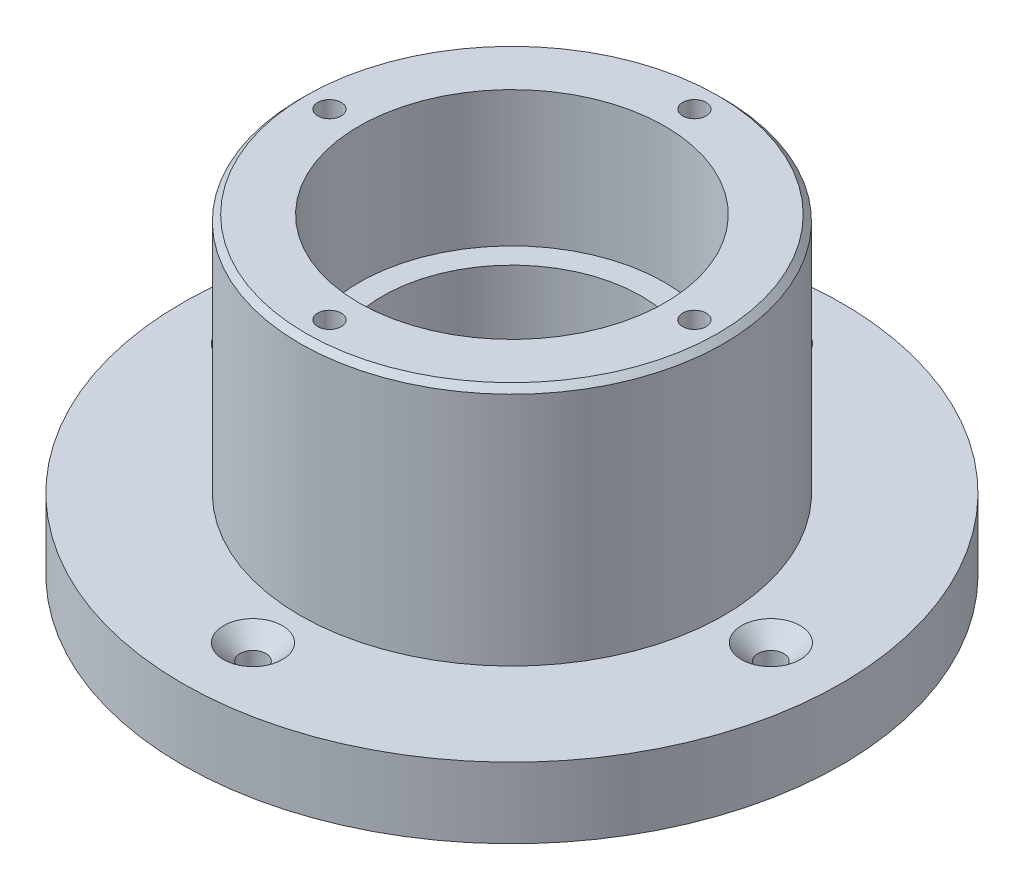
SolidWorks part; units mm, degrees
material "ABS"
ref_plane "Спереди" through (0, 0, 0) normal (0, 0, 1) x (1, 0, 0)
ref_plane "Сверху" through (0, 0, 0) normal (0, 1, 0) x (1, 0, 0)
ref_plane "Справа" through (0, 0, 0) normal (1, 0, 0) x (0, 0, -1)
sketch "Эскиз1" plane through (0, 0, 0) normal (0, 1, 0) x (1, 0, 0)
  circle A0 centre (0, 0) radius 26
  dimension "D1" = 52
extrude "Бобышка-Вытянуть1" add sketch "Эскиз1" along normal blind 4
sketch "Эскиз2" plane through (0, 4, 0) normal (0, 1, 0) x (1, 0, 0)
  circle A0 centre (0, 0) radius 18
  dimension "D1" = 36
extrude "Бобышка-Вытянуть2" add sketch "Эскиз2" along normal blind 20.5
sketch "Эскиз3" plane through (0, 24.5, 0) normal (0, 1, 0) x (1, 0, 0)
  circle A0 centre (0, 0) radius 13
  dimension "D1" = 26
extrude "Вырез-Вытянуть1" cut sketch "Эскиз3" along direction (0, 1, 0) on the side against the normal offset from surface (11.5 mm away) 13 up to face at (0, 0, 26)
sketch "Эскиз4" plane through (0, 4, 0) normal (0, 1, 0) x (1, 0, 0)
  circle A0 centre (0, 0) radius 22 construction
  circle A1 centre (-22, 0) radius 2.2
  circle A2 centre (0, 22) radius 2.2
  circle A3 centre (22, 0) radius 2.2
  circle A4 centre (0, -22) radius 2.2
  point P14 (0, 0)
  dimension "D1" = 44
  dimension "D2" = 4.4
  dimension "D3" = 4
sketch "Эскиз6" plane through (0, 13, 0) normal (0, 1, 0) x (1, 0, 0)
  circle A0 centre (0, 0) radius 11
  dimension "D1" = 22
extrude "Вырез-Вытянуть4" cut sketch "Эскиз6" against normal through all
sketch "Эскиз7" plane through (0, 24.5, 0) normal (0, 1, 0) x (1, 0, 0)
  circle A0 centre (0, 0) radius 15.5 construction
  circle A1 centre (-15.5, 0) radius 1
  circle A2 centre (0, 15.5) radius 1
  circle A3 centre (15.5, 0) radius 1
  circle A4 centre (0, -15.5) radius 1
  point P14 (0, 0)
  dimension "D1" = 31
  dimension "D2" = 2
extrude "Вырез-Вытянуть5" cut sketch "Эскиз7" against normal blind 5
sketch "Эскиз8" plane through (0, 4, 0) normal (0, 1, 0) x (1, 0, 0)
  circle A0 centre (0, 0) radius 26
  circle A1 centre (0, 0) radius 28
  dimension "D1" = 56
  dimension "D2" = 52
extrude "Бобышка-Вытянуть3" add sketch "Эскиз8" against normal blind 6
chamfer "Фаска1" distance 0.5 angle 45 1 edges at (0, -2, 26)
chamfer "Фаска2" distance 0.5 angle 45 1 edges at (0, 24.5, 18)
ref_axis "Ось1" through (0, -20.7688, 22) along (0, 1, 0)
sketch "Эскиз9" plane through (0, 0, 0) normal (1, 0, 0) x (0, 0, -1)
  line L1 (-22, -20.7688) -> (-22, 30.1347) construction
  line L2 (-20.9, 2.648) -> (-19.5, 4)
  line L3 (22, 4) -> (-22, 4) construction
  line L4 (-19.5, 4) -> (-22, 4)
  line L5 (-19.8, 4) -> (-24.2, 4) construction
  line L6 (-22, 2.648) -> (-22, 4)
  line L7 (-20.9, 2.648) -> (-20.9, -2)
  line L8 (-28, -2) -> (28, -2) construction
  line L9 (-20.9, -2) -> (-22, -2)
  line L10 (-22, -2) -> (-22, 2.648)
  dimension "D1" = 1.1
  dimension "D2" = 2.5
  dimension "D3" = 46
revolve "Вырез-Повернуть2" cut sketch "Эскиз9" angle 360 about axis through (0, -20.7688, 22) along (0, 1, 0)
pattern_circular "Круговой массив1" count 4 over 360 about axis through (0, 24.5, 0) along (0, -1, 0) of "Вырез-Повернуть2"
